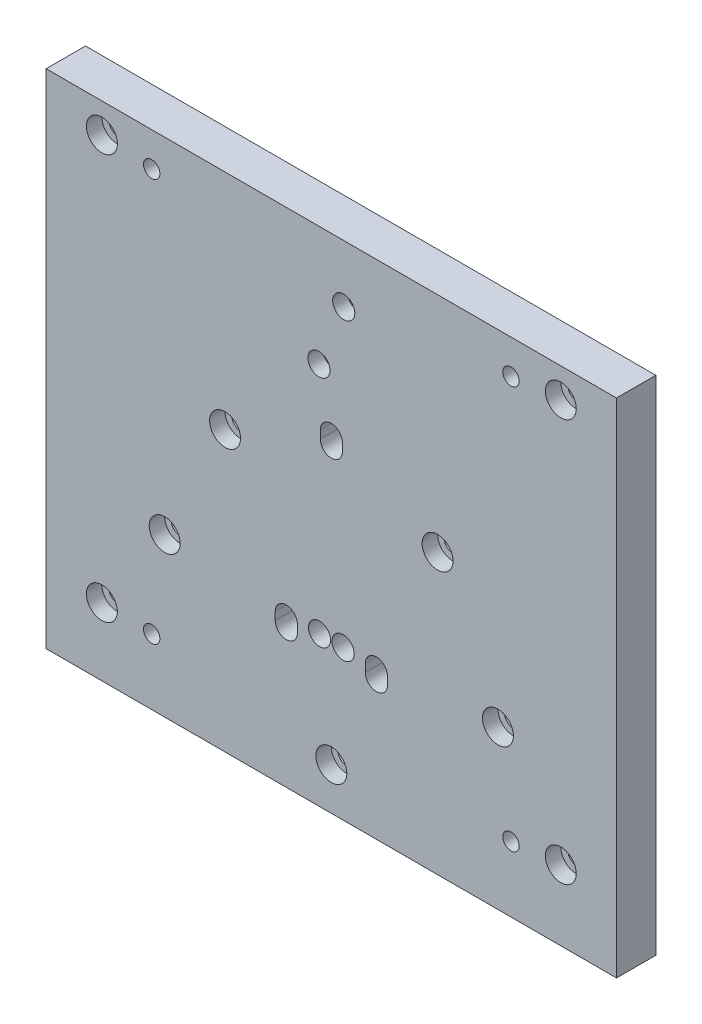
SolidWorks part; units mm, degrees
material "Beech"
ref_plane "Front Plane" through (0, 0, 0) normal (0, 0, 1) x (1, 0, 0)
ref_plane "Top Plane" through (0, 0, 0) normal (0, 1, 0) x (1, 0, 0)
ref_plane "Right Plane" through (0, 0, 0) normal (1, 0, 0) x (0, 0, -1)
sketch "Sketch1" plane through (0, 0, 0) normal (0, 0, 1) x (1, 0, 0)
  line L1 (2.065, -202.025) -> (-182.085, -202.025)
  line L2 (2.065, -202.025) -> (2.065, -55.975)
  line L3 (2.065, -55.975) -> (-182.085, -55.975)
  line L4 (-182.085, -202.025) -> (-182.085, -55.975)
  line L5 (2.065, -202.025) -> (-182.085, -55.975) construction
  line L6 (2.065, -55.975) -> (-182.085, -202.025) construction
  point P0 (-90.01, -129)
  dimension "D1" = 184.15
  dimension "D2" = 146.05
extrude "Boss-Extrude1" add sketch "Sketch1" along normal blind 12.7
ref_plane "CL" through (0, -129, 0) normal (0, -1, 0) x (-1, 0, 0)
sketch "Sketch5" plane through (0, -202.025, 0) normal (0, -1, 0) x (1, 0, 0)
  line L4 (-182.085, 0) -> (2.065, 0)
  line L5 (2.065, 0) -> (2.065, 12.7)
  line L6 (2.065, 12.7) -> (-182.085, 12.7)
  line L7 (-182.085, 12.7) -> (-182.085, 0)
  line L8 (-182.085, 0) -> (2.065, 0)
  line L9 (2.065, 0) -> (2.065, 12.7)
  line L10 (2.065, 12.7) -> (-182.085, 12.7)
  line L11 (-182.085, 12.7) -> (-182.085, 0)
  dimension "D1" = 0
extrude "Boss-Extrude2" add sketch "Sketch5" along normal up to surface (16.125 mm away)
hole_wizard "CBORE for M5 SHCS2" positions "Sketch2" profile "Sketch3" counterbore size "M5" standard "ANSI Metric" end condition up to next
sketch "Sketch2" plane through (0, 0, 12.7) normal (0, 0, 1) x (1, 0, 0)
  point P0 (-55.7, -127.9887)
  point P2 (-124.32, -127.9887)
  point P17 (-90.01, -204.5313)
  point P19 (-143.8109, -167.1)
  point P21 (-36.2091, -167.1)
sketch "Sketch3" plane through (-55.7, -127.9887, 12.7) normal (1, 0, 0) x (0, -1, 0)
  line L0 (0, 0) -> (0, 12.7)
  line L1 (0, 12.7) -> (2.9, 12.7)
  line L3 (2.9, 12.7) -> (2.9, 5)
  line L4 (2.9, 5) -> (5, 5)
  line L5 (5, 5) -> (5, 0)
  line L7 (5, 0) -> (0, 0)
  line L11 (0, -6.35) -> (0, 107.95) construction
  dimension "Thru Hole Dia." = 5.8
  dimension "Thru Hole Depth" = 12.7
  dimension "C'Bore Dia." = 10
  dimension "C'Bore Depth" = 5
hole_wizard "CBORE for M5 SHCS3" positions "Sketch6" profile "Sketch7" counterbore size "M5" standard "ANSI Metric" end condition through all
sketch "Sketch6" plane through (0, 0, 12.7) normal (0, 0, 1) x (1, 0, 0)
  point P0 (-15.925, -65.5)
  point P2 (-15.925, -195.4887)
  point P4 (-164.095, -196.2787)
  point P6 (-164.095, -65.5)
sketch "Sketch7" plane through (-15.925, -65.5, 12.7) normal (1, 0, 0) x (0, -1, 0)
  line L0 (0, 0) -> (0, 12.7)
  line L1 (0, 12.7) -> (2.65, 12.7)
  line L3 (2.65, 12.7) -> (2.65, 5)
  line L4 (2.65, 5) -> (5, 5)
  line L5 (5, 5) -> (5, 0)
  line L7 (5, 0) -> (0, 0)
  line L11 (0, -6.35) -> (0, 107.95) construction
  dimension "Thru Hole Dia." = 5.3
  dimension "Thru Hole Depth" = 12.7
  dimension "C'Bore Dia." = 10
  dimension "C'Bore Depth" = 5
sketch "Sketch12" plane through (0, 0, 0) normal (0, 0, -1) x (-1, 0, 0)
  circle A0 centre (164.095, -65.5) radius 5
  circle A1 centre (164.095, -196.2787) radius 5
  dimension "D1" = 10
extrude "Cut-Extrude1" cut sketch "Sketch12" against normal blind 2.54
hole_wizard "CBORE SLOT for #6 Socket Head Cap Screw1" positions "Sketch15" profile "Sketch16" size "#6" standard "ANSI Inch" slot yes end condition through all
sketch "Sketch15" plane through (0, 0, 12.7) normal (0, 0, 1) x (1, 0, 0)
  line L0 (-90.01, -117.15) -> (-90.01, -110.8) construction
  line L1 (-90.01, -218.15) -> (-90.01, -55.975) construction
  line L2 (-182.085, -218.15) -> (2.065, -218.15) construction
  line L3 (2.065, -55.975) -> (-182.085, -55.975) construction
  point P0 (-90.01, -113.975)
  point P6 (-104.5514, -171.9951)
  point P17 (-75.4686, -171.9951)
  dimension "D1" = 6.35
sketch "Sketch16" plane through (-90.01, -113.975, 12.7) normal (1, 0, 0) x (0, -1, 0)
  line L0 (0, 0) -> (0, 12.7)
  line L1 (0, 12.7) -> (1.8986, 12.7)
  line L3 (1.8986, 12.7) -> (1.8986, 7.3152)
  line L4 (1.8986, 7.3152) -> (3.5725, 7.3152)
  line L5 (3.5725, 7.3152) -> (3.5725, 0)
  line L7 (3.5725, 0) -> (0, 0)
  line L11 (0, -6.35) -> (0, 107.95) construction
  dimension "Thru Hole Dia." = 3.7973
  dimension "Thru Hole Depth" = 12.7
  dimension "C'Bore Dia." = 7.145
  dimension "C'Bore Depth" = 7.3152
hole_wizard "CBORE for #6 Socket Head Cap Screw1" positions "Sketch19" profile "Sketch18" counterbore size "#6" standard "ANSI Inch" end condition through all
sketch "Sketch19" plane through (0, 0, 12.7) normal (0, 0, 1) x (1, 0, 0)
  line L0 (-90.01, -218.15) -> (-90.01, -55.975) construction
  line L1 (-182.085, -218.15) -> (2.065, -218.15) construction
  line L2 (2.065, -55.975) -> (-182.085, -55.975) construction
  point P0 (-93.82, -169.8501)
  point P15 (-86.2, -169.8501)
  dimension "D1" = 48.2999
  dimension "D2" = 3.81
sketch "Sketch18" plane through (-93.82, -169.8501, 12.7) normal (1, 0, 0) x (0, -1, 0)
  line L0 (0, 0) -> (0, 12.7)
  line L1 (0, 12.7) -> (2.1526, 12.7)
  line L3 (2.1526, 12.7) -> (2.1526, 7.3152)
  line L4 (2.1526, 7.3152) -> (3.5725, 7.3152)
  line L5 (3.5725, 7.3152) -> (3.5725, 0)
  line L7 (3.5725, 0) -> (0, 0)
  line L11 (0, -6.35) -> (0, 107.95) construction
  dimension "Thru Hole Dia." = 4.3053
  dimension "Thru Hole Depth" = 12.7
  dimension "C'Bore Dia." = 7.145
  dimension "C'Bore Depth" = 7.3152
hole_wizard "M5 Clearance Hole1" positions "Sketch20" profile "Sketch21" hole size "M5" standard "ANSI Metric" end condition through all
sketch "Sketch20" plane through (0, 0, 12.7) normal (0, 0, 1) x (1, 0, 0)
  point P0 (-32.01, -66.9887)
  point P4 (-148.01, -66.9887)
  point P6 (-148.01, -196.9887)
  point P8 (-32.01, -196.9887)
sketch "Sketch21" plane through (-32.01, -66.9887, 12.7) normal (1, 0, 0) x (0, -1, 0)
  line L0 (0, 0) -> (0, 12.7)
  line L1 (0, 12.7) -> (2.65, 12.7)
  line L2 (2.65, 12.7) -> (2.65, 0)
  line L5 (2.65, 0) -> (0, 0)
  line L11 (0, -6.35) -> (0, 107.95) construction
  dimension "Thru Hole Dia." = 5.3
  dimension "Thru Hole Depth" = 12.7
hole_wizard "CBORE for #6 Socket Head Cap Screw2" positions "Sketch22" profile "Sketch23" counterbore size "#6" standard "ANSI Inch" end condition through all
sketch "Sketch22" plane through (0, 0, 12.7) normal (0, 0, 1) x (1, 0, 0)
  point P0 (-94.01, -94.5397)
  point P2 (-86.01, -74.5397)
sketch "Sketch23" plane through (-94.01, -94.5397, 12.7) normal (1, 0, 0) x (0, -1, 0)
  line L0 (0, 0) -> (0, 12.7)
  line L1 (0, 12.7) -> (2.1527, 12.7)
  line L3 (2.1527, 12.7) -> (2.1526, 4.7752)
  line L4 (2.1526, 4.7752) -> (3.5725, 4.7752)
  line L5 (3.5725, 4.7752) -> (3.5725, 0)
  line L7 (3.5725, 0) -> (0, 0)
  line L11 (0, -6.35) -> (0, 107.95) construction
  dimension "Thru Hole Dia." = 4.3053
  dimension "Thru Hole Depth" = 12.7
  dimension "C'Bore Dia." = 7.145
  dimension "C'Bore Depth" = 4.7752
